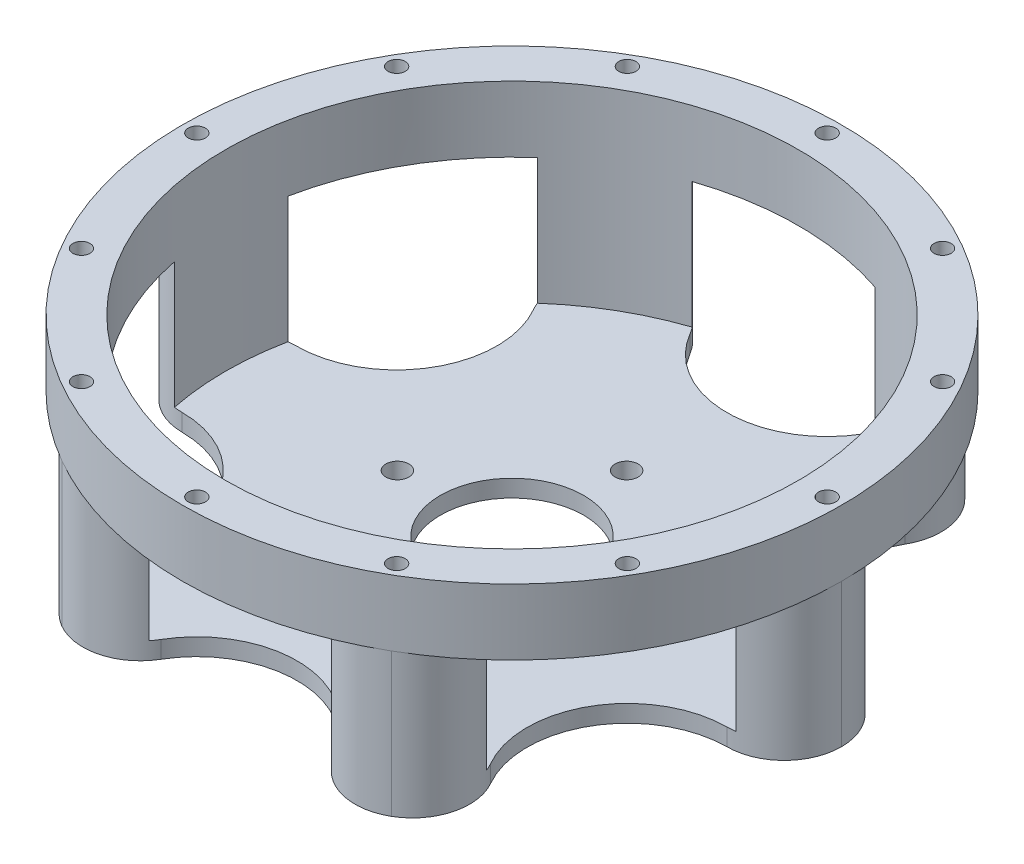
SolidWorks part; units mm, degrees
ref_plane "Front Plane" through (0, 0, 0) normal (0, 0, 1) x (1, 0, 0)
ref_plane "Top Plane" through (0, 0, 0) normal (0, 1, 0) x (1, 0, 0)
ref_plane "Right Plane" through (0, 0, 0) normal (1, 0, 0) x (0, 0, -1)
sketch "Sketch1" plane through (0, 0, 0) normal (0, 1, 0) x (1, 0, 0)
  circle A0 centre (0, 0) radius 57.5
  circle A1 centre (0, 0) radius 55 construction
  circle A2 centre (55, 0) radius 1.5
  circle A3 centre (47.6314, -27.5) radius 1.5
  circle A4 centre (27.5, -47.6314) radius 1.5
  circle A5 centre (0, -55) radius 1.5
  circle A6 centre (-27.5, -47.6314) radius 1.5
  circle A7 centre (-47.6314, -27.5) radius 1.5
  circle A8 centre (-55, 0) radius 1.5
  circle A9 centre (-47.6314, 27.5) radius 1.5
  circle A10 centre (-27.5, 47.6314) radius 1.5
  circle A11 centre (0, 55) radius 1.5
  circle A12 centre (27.5, 47.6314) radius 1.5
  circle A13 centre (47.6314, 27.5) radius 1.5
  point P31 (0, 0)
  dimension "D1" = 115
  dimension "D2" = 110
  dimension "D3" = 3
  dimension "D4" = 12
extrude "Boss-Extrude1" add sketch "Sketch1" along normal blind 36.5
sketch "Sketch2" plane through (0, 36.5, 0) normal (0, 1, 0) x (1, 0, 0)
  circle A0 centre (0, 0) radius 50
  dimension "D1" = 100
extrude "Cut-Extrude1" cut sketch "Sketch2" against normal blind 33.5
sketch "Sketch3" plane through (0, 0, 0) normal (0, -1, 0) x (1, 0, 0)
  circle A0 centre (0, 0) radius 55 construction
  circle A1 centre (0, 55) radius 17.5
  dimension "D1" = 35
extrude "Cut-Extrude2" cut sketch "Sketch3" against normal blind 25
fillet "Fillet1" radius 10 2 edges at (-17.4985, 12.5, 54.7727) (17.4985, 12.5, 54.7727)
pattern_circular "CirPattern2" count 6 over 360 about axis through (0, 3, 0) along (0, 1, 0) of "Cut-Extrude2", "Fillet1" reverse direction yes
sketch "Sketch5" plane through (0, 0, 0) normal (0, -1, 0) x (1, 0, 0)
  circle A0 centre (0, 0) radius 20 construction
  circle A1 centre (0, 20) radius 2
  circle A2 centre (20, 0) radius 2
  circle A3 centre (0, -20) radius 2
  circle A4 centre (-20, 0) radius 2
  circle A5 centre (0, 0) radius 12.5
  point P14 (0, 0)
  dimension "D1" = 40
  dimension "D2" = 4
  dimension "D4" = 25
  dimension "D3" = 4
extrude "Cut-Extrude3" cut sketch "Sketch5" against normal blind 25
